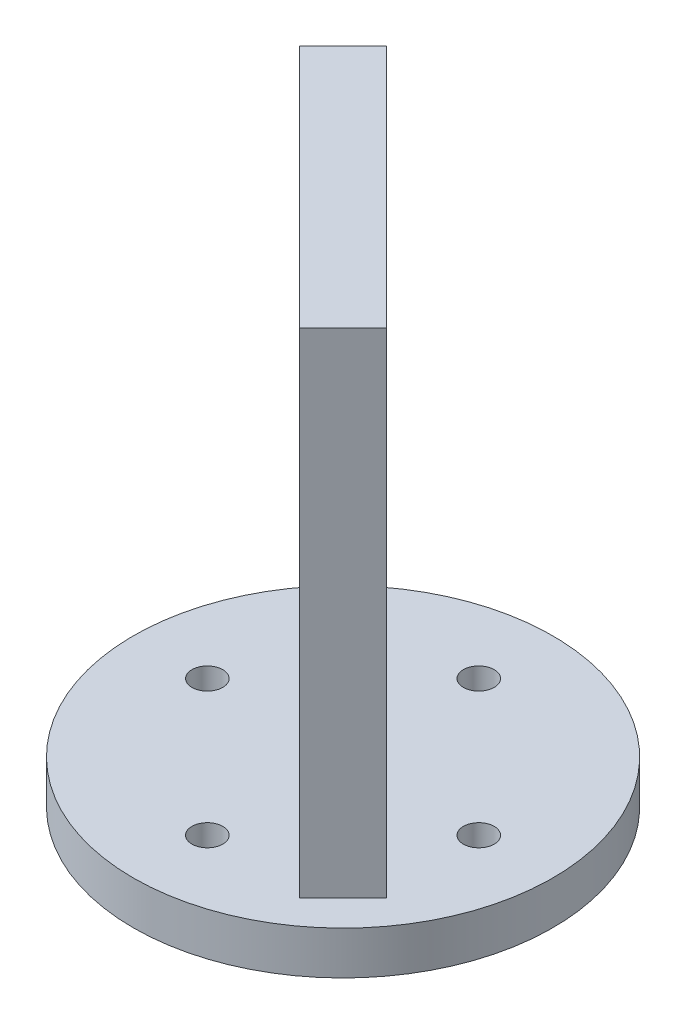
SolidWorks part; units mm, degrees
ref_plane "前视基准面" through (0, 0, 0) normal (0, 0, 1) x (1, 0, 0)
ref_plane "上视基准面" through (0, 0, 0) normal (0, 1, 0) x (1, 0, 0)
ref_plane "右视基准面" through (0, 0, 0) normal (1, 0, 0) x (0, 0, -1)
sketch "草图1" plane through (0, 0, 0) normal (0, 1, 0) x (1, 0, 0)
  circle A0 centre (0, 0) radius 34
extrude "凸台-拉伸1" add sketch "草图1" along normal blind 7
sketch "草图2" plane through (0, 7, 0) normal (0, 1, 0) x (1, 0, 0)
  circle A0 centre (22, 0) radius 2.5
  circle A1 centre (0, -22) radius 2.5
  circle A2 centre (-22, 0) radius 2.5
  circle A3 centre (0, 22) radius 2.5
  point P11 (0, 0)
  dimension "D1" = 4
extrude "切除-拉伸1" cut sketch "草图2" against normal blind 7
sketch "草图3" plane through (0, 7, 0) normal (0, 1, 0) x (1, 0, 0)
  line L0 (0, 0) -> (19.799, -19.799)
  line L1 (0, 0) -> (-19.799, 19.799)
  line L2 (-19.799, 19.799) -> (-16.2635, 23.3345)
  line L3 (19.799, -19.799) -> (16.2635, -23.3345)
  line L4 (-16.2635, 23.3345) -> (23.3345, -16.2635)
  line L5 (23.3345, -16.2635) -> (19.799, -19.799)
  line L6 (16.2635, -23.3345) -> (-23.3345, 16.2635)
  line L7 (-23.3345, 16.2635) -> (-19.799, 19.799)
extrude "凸台-拉伸2" add sketch "草图3" along normal blind 40 contours L7 L6 L3 L0 L1 | L5 L4 L2 L1 L0 region at (1.7678, 7, -1.7678) region at (-1.7678, 7, 1.7678)
sketch "草图4" plane through (-3.5355, 0, 3.5355) normal (-0.7071, 0, 0.7071) x (0.7071, 0, 0.7071)
  line L1 (-28, 7) -> (28, 7)
  line L2 (-28, 7) -> (-28, 87)
  line L3 (-28, 87) -> (28, 87)
  line L4 (28, 7) -> (28, 87)
extrude "凸台-拉伸3" add sketch "草图4" against normal blind 10
